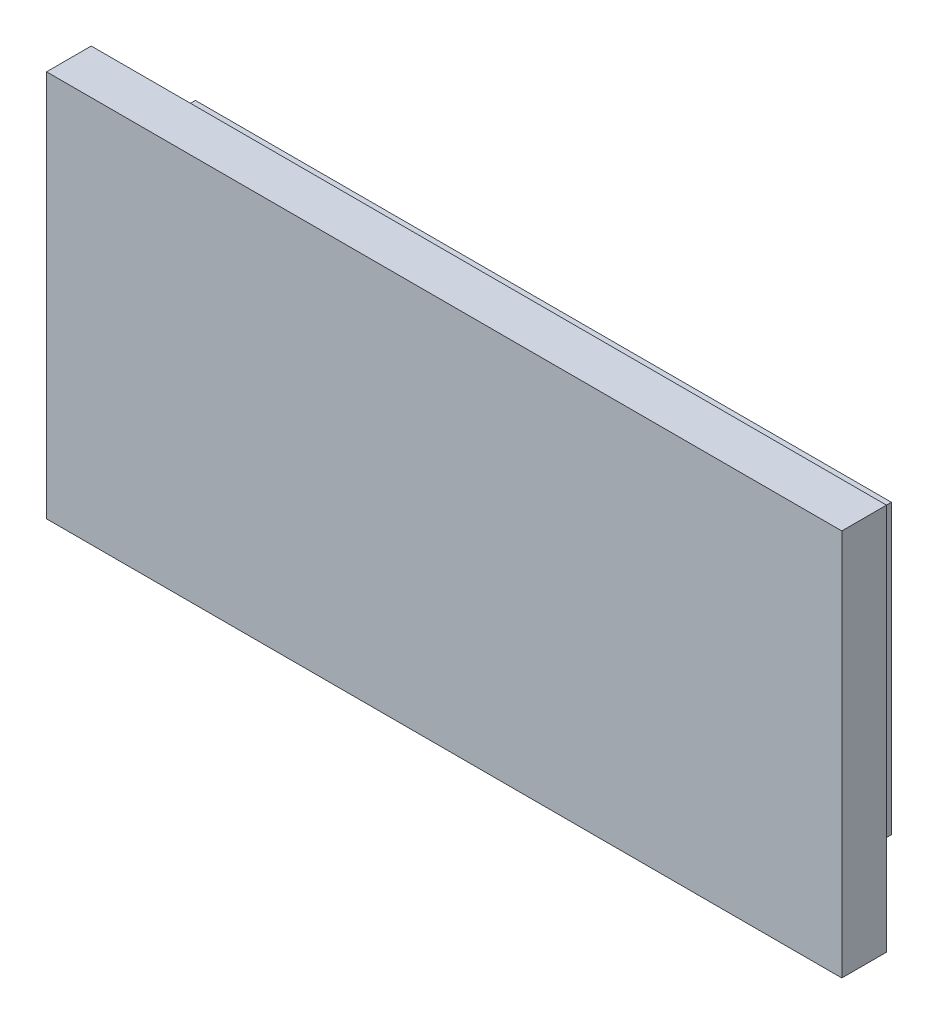
SolidWorks part; units mm, degrees
material "Custom Plastic"
ref_plane "Front Plane" through (0, 0, 0) normal (0, 0, 1) x (1, 0, 0)
ref_plane "Top Plane" through (0, 0, 0) normal (0, 1, 0) x (1, 0, 0)
ref_plane "Right Plane" through (0, 0, 0) normal (1, 0, 0) x (0, 0, -1)
sketch "Sketch1" plane through (0, 0, 0) normal (0, 0, 1) x (1, 0, 0)
  line L0 (-120.5087, -97.1518) -> (-106.2879, -97.1518) construction
  line L1 (-121.4087, -96.2518) -> (-105.3879, -96.2518)
  line L2 (-121.4087, -96.2518) -> (-121.4087, -104.0518)
  line L3 (-121.4087, -104.0518) -> (-105.3879, -104.0518)
  line L4 (-105.3879, -96.2518) -> (-105.3879, -104.0518)
  line L5 (-120.4087, -97.2518) -> (-106.3879, -97.2518)
  line L6 (-120.4087, -97.2518) -> (-120.4087, -103.0518)
  line L7 (-120.4087, -103.0518) -> (-106.3879, -103.0518)
  line L8 (-106.3879, -97.2518) -> (-106.3879, -103.0518)
  line L9 (-106.2879, -97.1518) -> (-106.2879, -103.1518) construction
  line L11 (-121.5087, -96.1518) -> (-121.5087, -104.1518) construction
  line L12 (-121.5087, -104.1518) -> (-105.2879, -104.1518) construction
  line L13 (-121.5087, -104.1518) -> (-105.2879, -104.1518) construction
  line L14 (-105.2879, -104.1518) -> (-105.2879, -96.1518) construction
  point P16 (-113.3983, -97.1518)
  point P17 (-113.3983, -97.2518)
  point P18 (-106.2879, -100.1518)
  point P19 (-106.3879, -100.1518)
  point P24 (-121.5087, -100.1518)
  point P25 (-121.4087, -100.1518)
  point P28 (-113.3983, -104.1518)
  point P29 (-113.3983, -104.0518)
  dimension "D1" = 0.1
  dimension "D2" = 0.1
  dimension "D3" = 0.1
  dimension "D4" = 0.1
extrude "Boss-Extrude1" add sketch "Sketch1" against normal blind 0.9 contours L4 L1 L2 L3 L5 L8 L7 L6 | L8 L5 L6 L7 region at (-113.3983, -96.43, 0) region at (-113.3983, -100.1518, 0)
extrude "Boss-Extrude2" add sketch "Sketch1<4>" against normal offset from surface (1.1 mm away) 10 from surface contours L8 L5 L6 L7 region at (-113.3983, -100.1518, 0) starting at face at (-113.3983, -100.1518, -0.9)
sketch "Sketch1<4>" plane through (0, 0, 0) normal (0, 0, 1) x (1, 0, 0) same geometry as "Sketch1"
